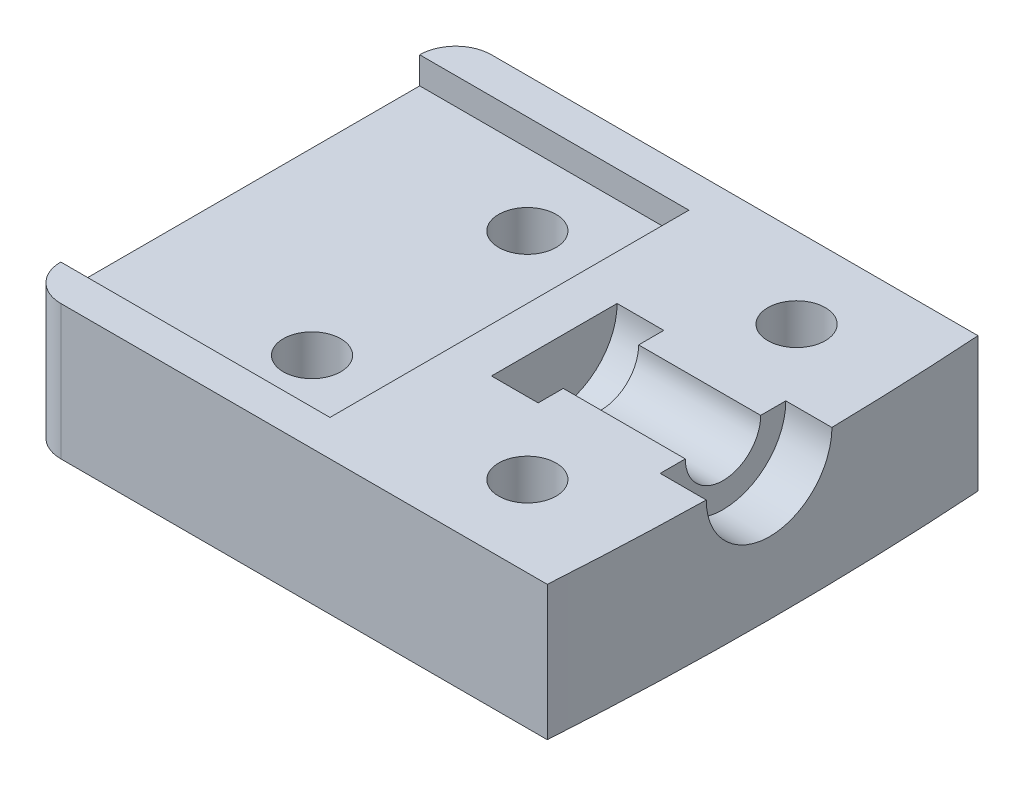
SolidWorks part; units mm, degrees
ref_plane "Front Plane" through (0, 0, 0) normal (0, 0, 1) x (1, 0, 0)
ref_plane "Top Plane" through (0, 0, 0) normal (0, 1, 0) x (1, 0, 0)
ref_plane "Right Plane" through (0, 0, 0) normal (1, 0, 0) x (0, 0, -1)
sketch "Sketch1" plane through (0, 0, 0) normal (0, 1, 0) x (1, 0, 0)
  line L0 (0, 0) -> (-180, 0) construction
  line L1 (0, -12) -> (-25, -12)
  line L2 (0, -12) -> (0, 12)
  line L3 (0, 12) -> (-25, 12)
  line L4 (-25, -12) -> (-25, 12)
  line L5 (-180, 0) -> (4.5, 0) construction
  line L6 (0, 12) -> (4.1093, 12)
  line L7 (0, -12) -> (4.1093, -12)
  line L8 (-180, 0) -> (5, 0) construction
  arc A0 (4.1093, -12) -> (4.1093, 12) centre (-180, 0) ccw
  circle A1 centre (-180, 0) radius 185 construction
  point P4 (0, 0)
  dimension "D4" = 184.5
  dimension "D5" = 185
  dimension "D1" = 25
  dimension "D2" = 24
  dimension "D3" = 180
extrude "Boss-Extrude1" add sketch "Sketch1" along normal blind 10 contours L4 L1 L2 L3 | L7 A0 L6 L2 region at (-12.5, 0, 0) region at (2.1865, 0, 0)
sketch "Sketch2" plane through (0, 10, 0) normal (0, 1, 0) x (1, 0, 0)
  line L1 (-25, -12) -> (-25, 12) construction
  line L2 (-25, 10) -> (-10, 10)
  line L3 (-25, 10) -> (-25, -10)
  line L4 (-25, -10) -> (-10, -10)
  line L5 (-10, 10) -> (-10, -10)
  point P0 (-25, 0)
  point P7 (-25, 0)
  dimension "D1" = 20
  dimension "D2" = 15
extrude "Cut-Extrude1" cut sketch "Sketch2" against normal blind 1.5
sketch "Sketch3" plane through (0, 10, 0) normal (0, 1, 0) x (1, 0, 0)
  line L0 (5, 0) -> (-7.5, 0) construction
  line L1 (0, 0) -> (-180, 0) construction
  dimension "D1" = 12.5
ref_plane "shaft" through (-7.5, 0, 0) normal (1, 0, 0) x (0, 0, -1)
sketch "Sketch4" plane through (-7.5, 0, 0) normal (1, 0, 0) x (0, 0, -1)
  line L0 (12, 10) -> (-12, 10) construction
  circle A0 centre (0, 10) radius 2.1
  dimension "D1" = 4.2
extrude "Cut-Extrude2" cut sketch "Sketch4" along normal through all
fillet "Fillet1" radius 2 2 edges at (-25, 5, -12) (-25, 5, 12)
sketch "Sketch5" plane through (-7.5, 0, 0) normal (1, 0, 0) x (0, 0, -1)
  line L0 (-2.1, 10) -> (2.1, 10) construction
  circle A0 centre (0, 10) radius 3.5
  dimension "D1" = 7
extrude "Cut-Extrude3" cut sketch "Sketch5" along normal blind 2.6
sketch "Sketch7" plane through (-7.5, 0, 0) normal (1, 0, 0) x (0, 0, -1)
  line L0 (-3.5, 10) -> (3.5, 10) construction
  circle A0 centre (0, 10) radius 2.5
  dimension "D1" = 5
extrude "Cut-Extrude4" [suppressed] cut sketch "Sketch7" against normal blind 0.2 and the other way blind 2.7
ref_plane "Plane2" through (0, 10, 0) normal (0, 1, 0) x (1, 0, 0)
sketch "Sketch8" plane through (0, 10, 0) normal (0, 1, 0) x (1, 0, 0)
  line L0 (0, 0) -> (4.5, 0) construction
  line L2 (1.9, 0) -> (4.5, 0)
  line L3 (1.9, 0) -> (1.9, 3.5)
  line L4 (1.9, 3.5) -> (4.5, 3.5)
  line L5 (4.5, 0) -> (4.5, 3.5)
  arc A0 (4.488, -2.1) -> (4.488, 2.1) centre (-180, 0) ccw construction
  dimension "D1" = 2.6
  dimension "D2" = 7
revolve "Cut-Revolve1" cut sketch "Sketch8" angle 360 about L0
sketch "Sketch9" plane through (1.9, 0, 0) normal (1, 0, 0) x (0, 0, -1)
  circle A0 centre (0, 10) radius 2.5
  dimension "D1" = 5
extrude "Cut-Extrude5" [suppressed] cut sketch "Sketch9" against normal up to surface (9.7 mm away) up to face at (-25, 4.25, 0)
sketch "Sketch11" plane through (0, 8.5, 0) normal (0, 1, 0) x (1, 0, 0)
  circle A0 centre (-15, -6) radius 1.5 construction
  circle A1 centre (-15, 6) radius 1.5 construction
  circle A2 centre (-15, -6) radius 1.5 construction
  circle A3 centre (-15, 6) radius 1.5 construction
hole_wizard "Ø3.2 (3.2) Diameter Hole2" positions "Sketch12" profile "Sketch13" hole size "Ø3.2" standard "ISO" end condition through all
sketch "Sketch12" plane through (0, 8.5, 0) normal (0, 1, 0) x (1, 0, 0)
  point P0 (-15, 6)
  point P3 (-15, -6)
sketch "Sketch13" plane through (-15, 8.5, -6) normal (1, 0, 0) x (0, 0, 1)
  line L0 (0, 0) -> (0, 8.5)
  line L1 (0, 8.5) -> (1.6, 8.5)
  line L2 (1.6, 8.5) -> (1.6, 0)
  line L5 (1.6, 0) -> (0, 0)
  line L11 (0, -6.35) -> (0, 107.95) construction
  dimension "Thru Hole Dia." = 3.2
  dimension "Thru Hole Depth" = 8.5
sketch "Sketch14" plane through (0, 10, 0) normal (0, 1, 0) x (1, 0, 0)
  line L0 (-10, 0) -> (0, 0) construction
  line L1 (-10, -10) -> (-10, 10) construction
  line L2 (-1.5, 12) -> (-1.5, -12) construction
  line L3 (4.1093, 12) -> (-23, 12) construction
  line L4 (4.1093, -12) -> (-23, -12) construction
  point P7 (-1.5, -7.5)
  point P13 (-1.5, 7.5)
  dimension "D1" = 8.5
  dimension "D2" = 15
hole_wizard "Ø3.2 (3.2) Diameter Hole1" positions "Sketch15" profile "Sketch16" hole size "Ø3.2" standard "ISO" end condition through all
sketch "Sketch15" plane through (0, 10, 0) normal (0, 1, 0) x (1, 0, 0)
  point P0 (-1.5, 7.5)
  point P3 (-1.5, -7.5)
sketch "Sketch16" plane through (-1.5, 10, -7.5) normal (1, 0, 0) x (0, 0, 1)
  line L0 (0, 0) -> (0, 10)
  line L1 (0, 10) -> (1.6, 10)
  line L2 (1.6, 10) -> (1.6, 0)
  line L5 (1.6, 0) -> (0, 0)
  line L11 (0, -6.35) -> (0, 107.95) construction
  dimension "Thru Hole Dia." = 3.2
  dimension "Thru Hole Depth" = 10
sketch "Sketch17" plane through (0, 0, 0) normal (0, -1, 0) x (1, 0, 0)
  line L3 (-25, 10) -> (-25, -10)
  line L4 (-23, -12) -> (4.1093, -12)
  line L5 (4.1093, 12) -> (-23, 12)
  line L6 (-25, 10) -> (-25, -10)
  line L7 (-23, -12) -> (4.1093, -12)
  line L8 (4.1093, 12) -> (-23, 12)
  arc A3 (-25, -10) -> (-23, -12) centre (-23, -10) ccw
  arc A4 (4.1093, -12) -> (4.1093, 12) centre (-180, 0) ccw
  arc A5 (-23, 12) -> (-25, 10) centre (-23, 10) ccw
  arc A6 (-25, -10) -> (-23, -12) centre (-23, -10) ccw
  arc A7 (4.1093, -12) -> (4.1093, 12) centre (-180, 0) ccw
  arc A8 (-23, 12) -> (-25, 10) centre (-23, 10) ccw
  dimension "D1" = 0
extrude "Cut-Extrude6" cut sketch "Sketch17" against normal blind 2.5
